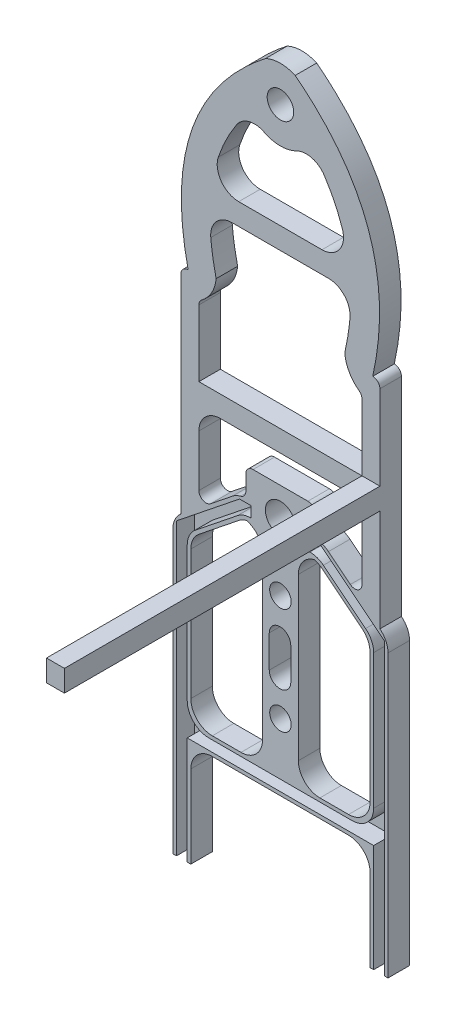
SolidWorks part; units mm, degrees
material "1023 Carbon Steel Sheet (SS)"
ref_plane "Front Plane" through (0, 0, 0) normal (0, 0, 1) x (1, 0, 0)
ref_plane "Top Plane" through (0, 0, 0) normal (0, 1, 0) x (1, 0, 0)
ref_plane "Right Plane" through (0, 0, 0) normal (1, 0, 0) x (0, 0, -1)
sketch "Sketch1" plane through (0, 0, 0) normal (0, 0, 1) x (1, 0, 0)
  line L0 (0, 0) -> (0, 162.6224) construction
  line L1 (0, 0) -> (0, -162.6224) construction
  line L2 (25, 0) -> (150, 0) construction
  line L3 (25, -200) -> (-25, -200)
  line L4 (25, -200) -> (25, -25)
  line L5 (25, 200) -> (-25, 200)
  line L6 (-25, -200) -> (-25, -25)
  line L7 (25, -200) -> (-25, 200) construction
  line L8 (25, 200) -> (-25, -200) construction
  line L9 (150, 0) -> (150, -400)
  line L10 (150, -400) -> (125, -400)
  line L11 (125, -400) -> (125, -25)
  line L12 (125, -25) -> (25, -25)
  line L13 (125, 0) -> (25, 0)
  line L14 (0, 200) -> (0, 285) construction
  line L15 (25, 0) -> (25, 200)
  line L16 (-150, -400) -> (-125, -400)
  line L17 (-125, -400) -> (-125, -25)
  line L18 (-125, -25) -> (-25, -25)
  line L19 (-150, 0) -> (-150, -400)
  line L20 (-125, 0) -> (-25, 0)
  line L21 (-25, 0) -> (-25, 200)
  line L22 (-125, 0) -> (-125, 225)
  line L23 (-125, 225) -> (-50, 285)
  line L24 (-50, 285) -> (50, 285)
  line L25 (125, 0) -> (125, 225)
  line L26 (125, 225) -> (50, 285)
  line L27 (-150, 0) -> (-150, 237.0156)
  line L28 (-150, 237.0156) -> (-58.7695, 310)
  line L29 (-58.7695, 310) -> (58.7695, 310)
  line L30 (150, 237.0156) -> (58.7695, 310)
  line L31 (150, 0) -> (150, 237.0156)
  circle A0 centre (0, 162.6224) radius 15
  circle A1 centre (0, -162.6224) radius 15
  dimension "D1" = 400
  dimension "D2" = 50
  dimension "D3" = 25
extrude "Boss-Extrude2" add sketch "Sketch1" along normal blind 30
sketch "Sketch2" plane through (0, 0, 30) normal (0, 0, 1) x (1, 0, 0)
  line L31 (145, -400) -> (145, 234.6125)
  line L32 (145, 234.6125) -> (57.0156, 305)
  line L33 (57.0156, 305) -> (-57.0156, 305)
  line L34 (-57.0156, 305) -> (-145, 234.6125)
  line L35 (-145, 234.6125) -> (-145, -400)
  line L36 (145, -400) -> (145, 234.6125)
  line L37 (145, 234.6125) -> (57.0156, 305)
  line L38 (57.0156, 305) -> (-57.0156, 305)
  line L39 (-57.0156, 305) -> (-145, 234.6125)
  line L40 (-145, 234.6125) -> (-145, -400)
  line L56 (130, 0) -> (130, 227.4031)
  line L57 (130, 227.4031) -> (51.7539, 290)
  line L58 (-130, 227.4031) -> (-130, 0)
  line L59 (-51.7539, 290) -> (-130, 227.4031)
  line L60 (51.7539, 290) -> (-51.7539, 290)
  line L61 (130, 0) -> (130, 227.4031)
  line L62 (130, 227.4031) -> (51.7539, 290)
  line L63 (-130, 227.4031) -> (-130, 0)
  line L64 (-51.7539, 290) -> (-130, 227.4031)
  line L65 (51.7539, 290) -> (-51.7539, 290)
  line L66 (-130, -400) -> (-130, -25)
  line L67 (-130, -400) -> (-130, -25)
  line L70 (130, -25) -> (130, -400)
  line L71 (130, -25) -> (130, -400)
  line L76 (-125, -5) -> (-25, -5)
  line L77 (-125, -5) -> (-25, -5)
  line L79 (-125, -20) -> (-25, -20)
  line L80 (-125, -20) -> (-25, -20)
  line L82 (25, -5) -> (125, -5)
  line L83 (25, -5) -> (125, -5)
  line L84 (-25, -5) -> (25, -5)
  line L85 (25, -20) -> (125, -20)
  line L86 (25, -20) -> (125, -20)
  line L87 (25, -20) -> (-25, -20)
  line L88 (-130, -25) -> (-130, -20)
  line L89 (-130, -20) -> (-125, -20)
  line L90 (-130, 0) -> (-130, -5)
  line L91 (-130, -5) -> (-125, -5)
  line L92 (130, 0) -> (130, -5)
  line L93 (130, -5) -> (125, -5)
  line L94 (130, -25) -> (130, -20)
  line L95 (130, -20) -> (125, -20)
  line L96 (-145, -400) -> (-130, -400)
  line L97 (130, -400) -> (145, -400)
  dimension "D1" = 5
  dimension "D2" = 5
  dimension "D3" = 5
  dimension "D4" = 5
  dimension "D5" = 5
  dimension "D6" = 5
  dimension "D7" = 5
  dimension "D8" = 5
extrude "Cut-Extrude1" cut sketch "Sketch2" against normal blind 25
sketch "Sketch5" plane through (0, 0, 30) normal (0, 0, 1) x (1, 0, 0)
  line L1 (-25, 200) -> (25, 200)
  line L2 (-25, 200) -> (-25, 0)
  line L3 (-25, 0) -> (25, 0)
  line L4 (25, 200) -> (25, 0)
  line L5 (-25, 200) -> (25, 0) construction
  line L6 (-25, 0) -> (25, 200) construction
  line L7 (-25, -25) -> (25, -25)
  line L8 (-25, -25) -> (-25, -200)
  line L9 (-25, -200) -> (25, -200)
  line L10 (25, -25) -> (25, -200)
  line L11 (-25, -25) -> (25, -200) construction
  line L12 (-25, -200) -> (25, -25) construction
  point P4 (0, 100)
  point P11 (0, -112.5)
extrude "Cut-Extrude2" cut sketch "Sketch5" against normal blind 30
fillet "Fillet12" radius 30 2 edges at (51.7539, 290, 17.5) (-51.7539, 290, 17.5)
sketch "Sketch6" plane through (0, 0, 0) normal (0, 0, -1) x (-1, 0, 0)
  line L0 (0, 0) -> (0, 285) construction
  line L1 (-50, 285) -> (50, 285) construction
  line L2 (0, 0) -> (25, 0)
  line L3 (125, 0) -> (-125, 0) construction
  line L4 (0, 285) -> (25, 285)
  line L5 (25, 285) -> (25, 0)
  line L6 (0, 285) -> (-25, 285)
  line L7 (-25, 285) -> (-25, 0)
  line L8 (-25, 0) -> (0, 0)
  line L9 (0, 0) -> (25, 0)
  line M19 (125, 0) -> (-125, 0)
  line M22 (-50, 285) -> (50, 285)
extrude "Boss-Extrude3" add sketch "Sketch6" against normal blind 30 contours L0 L7 M19 M22 | L0 L5 M19 M22 region at (12.5, 142.5, 0) region at (-12.5, 142.5, 0)
sketch "Sketch7" plane through (0, 0, 0) normal (0, 0, -1) x (-1, 0, 0)
  line L0 (-25, 142.5) -> (25, 142.5) construction
  line L1 (-25, 285) -> (-25, 0) construction
  line L2 (25, 285) -> (25, 0) construction
  line L3 (0, 142.5) -> (0, 216.75) construction
  circle A0 centre (0, 216.75) radius 15
  circle A1 centre (0, 68.25) radius 15
extrude "Cut-Extrude3" cut sketch "Sketch7" against normal blind 30
fillet "Fillet13" radius 30 14 edges at (150, 237.0156, 15) (58.7695, 310, 15) (-58.7695, 310, 15) (-150, 237.0156, 15) (-50, 285, 15) (-25, 285, 15) (-125, 225, 15) (-125, 0, 15) (-25, 0, 15) (25, 0, 15) (125, 0, 15) (125, 225, 15) (50, 285, 15) (25, 285, 15)
fillet "Fillet14" radius 30 4 edges at (-130, -5, 17.5) (130, -5, 17.5) (130, 227.4031, 17.5) (-130, 227.4031, 17.5)
sketch "Sketch8" plane through (0, 0, 30) normal (0, 0, 1) x (1, 0, 0)
  line L1 (14.3962, 104.0225) -> (-15.6038, 104.0225)
  line L2 (14.3962, 104.0225) -> (14.3962, 179.0225)
  line L3 (14.3962, 179.0225) -> (-15.6038, 179.0225)
  line L4 (-15.6038, 104.0225) -> (-15.6038, 179.0225)
  line L5 (14.3962, 104.0225) -> (-15.6038, 179.0225) construction
  line L6 (14.3962, 179.0225) -> (-15.6038, 104.0225) construction
  point P0 (-0.6038, 141.5225)
  dimension "D1" = 75
  dimension "D2" = 30
extrude "Cut-Extrude4" cut sketch "Sketch8" against normal blind 30
fillet "Fillet15" 2 edges at (-15.6038, 179.0225, 15) (14.3962, 179.0225, 15) type full round first side face at (-15.6038, 141.5225, 15) second side face at (14.3962, 141.5225, 15) middle face at (-0.6038, 179.0225, 15)
fillet "Fillet16" 2 edges at (-15.6038, 104.0225, 15) (14.3962, 104.0225, 15) type full round first side face at (-15.6038, 134.0225, 15) second side face at (14.3962, 134.0225, 15) middle face at (-0.6038, 104.0225, 15)
sketch "Sketch9" plane through (0, -400, 0) normal (0, -1, 0) x (1, 0, 0)
  line L1 (-166.6404, 60.6089) -> (172.1688, 60.6089)
  line L2 (-166.6404, 60.6089) -> (-166.6404, -36.5322)
  line L3 (-166.6404, -36.5322) -> (172.1688, -36.5322)
  line L4 (172.1688, 60.6089) -> (172.1688, -36.5322)
  line L5 (-166.6404, 60.6089) -> (172.1688, -36.5322) construction
  line L6 (-166.6404, -36.5322) -> (172.1688, 60.6089) construction
  point P4 (2.7642, 12.0384)
extrude "Cut-Extrude5" cut sketch "Sketch9" against normal blind 180
fillet "Fillet17" radius 30 2 edges at (125, -25, 15) (-125, -25, 15)
sketch "Sketch10" plane through (0, -220, 0) normal (0, -1, 0) x (1, 0, 0)
  line L1 (-161.1499, 58.9123) -> (166.5974, 58.9123)
  line L2 (-161.1499, 58.9123) -> (-161.1499, -30.2063)
  line L3 (-161.1499, -30.2063) -> (166.5974, -30.2063)
  line L4 (166.5974, 58.9123) -> (166.5974, -30.2063)
  line L5 (-161.1499, 58.9123) -> (166.5974, -30.2063) construction
  line L6 (-161.1499, -30.2063) -> (166.5974, 58.9123) construction
  point P4 (2.7237, 14.353)
extrude "Cut-Extrude6" cut sketch "Sketch10" against normal blind 50
sketch "Sketch11" plane through (0, 0, 0) normal (0, 0, -1) x (-1, 0, 0)
  line L0 (0, 68.25) -> (0, 309.75) construction
  line L2 (-48.2461, 310) -> (48.2461, 310)
  line L3 (-48.2461, 310) -> (-48.2461, 350)
  line L4 (-48.2461, 350) -> (48.2461, 350)
  line L5 (48.2461, 310) -> (48.2461, 350)
  line L6 (-48.2461, 310) -> (48.2461, 350) construction
  line L7 (-48.2461, 350) -> (48.2461, 310) construction
  point P8 (0, 330)
extrude "Boss-Extrude5" add sketch "Sketch11" against normal blind 30
sketch "Sketch12" plane through (0, 0, 0) normal (0, 0, -1) x (-1, 0, 0)
  line L0 (0, 68.25) -> (0, 309.75) construction
  circle A0 centre (0, 309.75) radius 15
extrude "Cut-Extrude7" cut sketch "Sketch12" against normal blind 30
fillet "Fillet18" radius 10 4 edges at (-48.2461, 310, 15) (48.2461, 310, 15) (48.2461, 350, 15) (-48.2461, 350, 15)
sketch "Sketch13" plane through (0, 0, 0) normal (0, 0, -1) x (-1, 0, 0)
  line L0 (138.7409, 246.0229) -> (138.7409, 546.0229)
  line L1 (138.7409, 546.0229) -> (-138.7409, 546.0229)
  line L2 (-138.7409, 546.0229) -> (-138.7409, 246.0229)
  line L3 (113.7409, 266.0229) -> (113.7409, 521.0229)
  line L4 (113.7409, 521.0229) -> (-113.7409, 521.0229)
  line L5 (-113.7409, 521.0229) -> (-113.7409, 266.0229)
  line L6 (-138.7409, 246.0229) -> (-113.7409, 266.0229)
  line L7 (-138.7409, 246.0229) -> (-66.9869, 303.4261) construction
  line L8 (138.7409, 246.0229) -> (113.7409, 266.0229)
  line L9 (-113.7409, 521.0229) -> (-113.7409, 246.0229) construction
  line L10 (66.9869, 303.4261) -> (138.7409, 246.0229) construction
  line L12 (113.7409, 246.0229) -> (113.7409, 521.0229) construction
  dimension "D1" = 25
extrude "Boss-Extrude6" add sketch "Sketch13" against normal blind 30
fillet "Fillet19" radius 10 6 edges at (-113.7409, 521.0229, 15) (113.7409, 521.0229, 15) (-113.7409, 266.0229, 15) (113.7409, 266.0229, 15) (138.7409, 546.0229, 15) (-138.7409, 546.0229, 15)
sketch "Sketch18" plane through (0, 0, 30) normal (0, 0, 1) x (1, 0, 0)
  line L0 (57.0156, 305) -> (14.2281, 305) construction
  line L1 (-41.2305, 290) -> (40.5901, 290)
  line L2 (-41.2305, 290) -> (-41.2305, 305)
  line L3 (-41.2305, 305) -> (40.5901, 305)
  line L4 (40.5901, 290) -> (40.5901, 305)
  line L5 (-41.2305, 290) -> (40.5901, 305) construction
  line L6 (-41.2305, 305) -> (40.5901, 290) construction
  point P5 (-0.3202, 297.5)
extrude "Boss-Extrude11" add sketch "Sketch18" against normal through all
sketch "Sketch19" plane through (0, 0, 30) normal (0, 0, 1) x (1, 0, 0)
  circle A0 centre (0, 309.75) radius 21
extrude "Cut-Extrude9" cut sketch "Sketch19" against normal blind 500
sketch "Sketch20" plane through (0, 0, 0) normal (0, 0, -1) x (-1, 0, 0)
  line L0 (0, 309.75) -> (0, 809.75) construction
  line L1 (-128.7409, 546.0229) -> (-89.7016, 546.0229)
  line L2 (128.7409, 546.0229) -> (-128.7409, 546.0229) construction
  line L3 (-89.7016, 546.0229) -> (-89.7016, 554.7373)
  line L4 (-89.7016, 546.0229) -> (-128.7409, 546.0229)
  line L5 (128.7409, 546.0229) -> (89.7016, 546.0229)
  line L6 (89.7016, 546.0229) -> (89.7016, 554.7373)
  line L7 (89.7016, 546.0229) -> (128.7409, 546.0229)
  circle A0 centre (0, 809.75) radius 18.5
  arc A1 (-41.1255, 781.3125) -> (41.1255, 781.3125) centre (0, 809.75) ccw
  arc A2 (20.5586, 855.3279) -> (-20.5586, 855.3279) centre (0, 809.75) ccw
  spline S0 degree 2 poles (-128.7409, 546.0229) (-171.5502, 737.8038) (-20.5586, 855.3279) knots 0 0 0 1 1 1
  spline S1 degree 1 poles (-89.7016, 554.7373) (4.0103, 823.7625) knots 0 0 1 1 construction
  spline S2 degree 2 poles (-89.7016, 554.7373) (-90.9196, 560.1935) (-94.038, 576.2757) (-97.4803, 602.1245) (-98.7089, 636.3275) (-94.8753, 672.5598) (-85.978, 706.2892) (-71.999, 737.9748) (-54.8609, 764.6672) (-43.0192, 779.1469) (-38.3331, 784.5192) (-28.6315, 795.1861) (-8.7665, 813.8107) (4.0103, 823.7625) knots 0 0 0 0.03125 0.09375 0.1875 0.3125 0.4375 0.5625 0.6875 0.784529 0.8125 0.831404 0.90625 1 1 1 only from (-89.7016, 554.7373) to (-41.1255, 781.3125)
  spline S3 degree 2 poles (128.7409, 546.0229) (171.5502, 737.8038) (20.5586, 855.3279) knots 0 0 0 1 1 1
  spline S4 degree 2 poles (89.7016, 554.7373) (90.9415, 560.1819) (94.1216, 576.2295) (97.6538, 602.0208) (98.9831, 636.1436) (95.2314, 672.2884) (86.3854, 705.9428) (72.4241, 737.5757) (55.1224, 764.4675) (43.4635, 778.6236) (41.1255, 781.3125) knots 0 0 0 0.03125 0.09375 0.1875 0.3125 0.4375 0.5625 0.6875 0.786375 0.809813 0.809813 0.809813
  dimension "D2" = 40
  dimension "D3" = 50
  dimension "D4" = 37
  dimension "D5" = 348.4129
  dimension "D1" = 500
extrude "Boss-Extrude12" add sketch "Sketch20" against normal blind 30 contours S4 L6 L5 S3 A2 S0 L1 L3 S2 A1 A0 region at (119.6042, 716.5586, 0)
sketch "Sketch21" plane through (0, 0, 30) normal (0, 0, 1) x (1, 0, 0)
  line L0 (113.7409, 286.8292) -> (113.7409, 511.0229) construction
  line L1 (113.7409, 388.3565) -> (138.7409, 388.3565)
  line L2 (113.7409, 388.3565) -> (113.7409, 418.3565)
  line L3 (113.7409, 418.3565) -> (138.7409, 418.3565)
  line L4 (138.7409, 388.3565) -> (138.7409, 418.3565)
  line L5 (113.7409, 388.3565) -> (138.7409, 418.3565) construction
  line L6 (113.7409, 418.3565) -> (138.7409, 388.3565) construction
  line L7 (138.7409, 536.0229) -> (138.7409, 246.0229) construction
  point P4 (126.2409, 403.3565)
  dimension "D1" = 30
extrude "Boss-Extrude13" add sketch "Sketch21" along normal blind 440
sketch "Sketch22" plane through (0, 0, 30) normal (0, 0, 1) x (1, 0, 0)
  line L0 (103.7409, 521.0229) -> (-103.7409, 521.0229) construction
  line L1 (-89.7016, 546.0229) -> (89.7016, 546.0229)
  line L2 (-89.7016, 546.0229) -> (-89.7016, 521.0229)
  line L3 (-89.7016, 521.0229) -> (89.7016, 521.0229)
  line L4 (89.7016, 546.0229) -> (89.7016, 521.0229)
  line L5 (-89.7016, 546.0229) -> (89.7016, 521.0229) construction
  line L6 (-89.7016, 521.0229) -> (89.7016, 546.0229) construction
  point P4 (0, 533.5229)
extrude "Cut-Extrude10" cut sketch "Sketch22" against normal blind 440
sketch "Sketch23" plane through (0, 0, 30) normal (0, 0, 1) x (1, 0, 0)
  line L2 (109.4987, 633.5071) -> (-109.7832, 633.5071)
  line L3 (109.4987, 633.5071) -> (109.4987, 663.5071)
  line L4 (109.4987, 663.5071) -> (-109.7832, 663.5071)
  line L5 (-109.7832, 633.5071) -> (-109.7832, 663.5071)
  line L6 (109.4987, 633.5071) -> (-109.7832, 663.5071) construction
  line L7 (109.4987, 663.5071) -> (-109.7832, 633.5071) construction
  point P6 (-0.1422, 648.5071)
  dimension "D1" = 30
extrude "Boss-Extrude14" add sketch "Sketch23" against normal blind 30
fillet "Fillet25" radius 50 2 edges at (89.7016, 521.0229, 15) (-89.7016, 521.0229, 15)
sketch "Sketch26" plane through (113.7409, 0, 0) normal (-1, 0, 0) x (0, 0, 1)
  line L0 (0, 286.8292) -> (0, 511.0229) construction
  line L1 (30, 418.3565) -> (0, 418.3565)
  line L2 (30, 418.3565) -> (30, 388.8146)
  line L3 (30, 388.8146) -> (0, 388.8146)
  line L4 (0, 418.3565) -> (0, 388.8146)
  line L5 (30, 418.3565) -> (0, 388.8146) construction
  line L6 (30, 388.8146) -> (0, 418.3565) construction
  point P4 (15, 403.5855)
extrude "Boss-Extrude16" add sketch "Sketch26" along normal up to next
fillet "Fillet26" radius 30 6 edges at (41.1255, 781.3125, 15) (-41.1255, 781.3125, 15) (-98.3822, 633.5071, 15) (98.1223, 633.5071, 15) (-95.9628, 663.5071, 15) (95.6635, 663.5071, 15)
fillet "Fillet28" radius 30 2 edges at (-113.7409, 388.8146, 15) (113.7409, 388.8146, 15)
